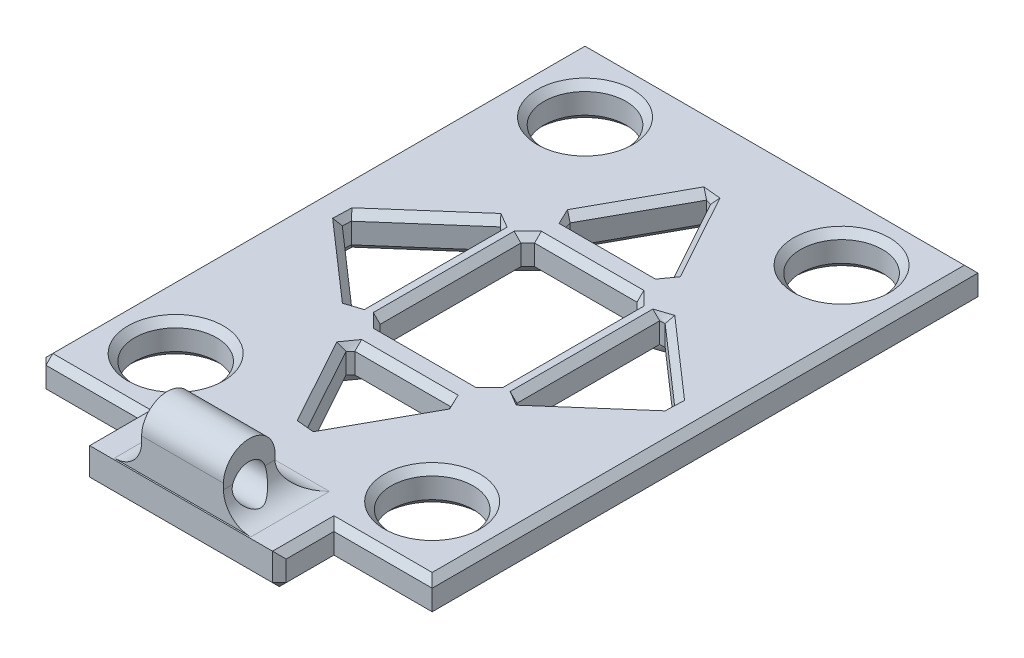
SolidWorks part; units mm, degrees
ref_plane "Front Plane" through (0, 0, 0) normal (0, 0, 1) x (1, 0, 0)
ref_plane "Top Plane" through (0, 0, 0) normal (0, 1, 0) x (1, 0, 0)
ref_plane "Right Plane" through (0, 0, 0) normal (1, 0, 0) x (0, 0, -1)
sketch "Sketch1" plane through (0, 0, 0) normal (0, 0, 1) x (1, 0, 0)
  line L1 (-18.288, 1.5875) -> (18.288, 1.5875)
  line L2 (-18.288, 1.5875) -> (-18.288, -1.5875)
  line L3 (-18.288, -1.5875) -> (18.288, -1.5875)
  line L4 (18.288, 1.5875) -> (18.288, -1.5875)
  line L5 (-18.288, 1.5875) -> (18.288, -1.5875) construction
  line L6 (-18.288, -1.5875) -> (18.288, 1.5875) construction
  point P0 (0, 0)
  dimension "D1" = 36.576
  dimension "D2" = 3.175
extrude "Boss-Extrude1" add sketch "Sketch1" along normal mid plane 50.8
sketch "Sketch2" plane through (0, 1.5875, 0) normal (0, 1, 0) x (1, 0, 0)
  line L0 (0, 25.4) -> (0, -26.1324) construction
  line L1 (-18.288, 0) -> (18.288, 0) construction
  line L4 (18.288, 25.4) -> (-18.288, 25.4)
  line L5 (-18.288, 25.4) -> (-18.288, -25.4)
  line L6 (-18.288, -25.4) -> (18.288, -25.4)
  line L7 (18.288, -25.4) -> (18.288, 25.4)
  line L8 (18.288, 25.4) -> (-18.288, 25.4)
  line L9 (-18.288, 25.4) -> (-18.288, -25.4)
  line L10 (-18.288, -25.4) -> (18.288, -25.4)
  line L11 (18.288, -25.4) -> (18.288, 25.4)
  circle A0 centre (-11.938, 19.05) radius 3.81
  circle A4 centre (-11.938, -19.05) radius 3.81
  circle A5 centre (11.938, -19.05) radius 3.81
  circle A6 centre (11.938, 19.05) radius 3.81
  point P11 (0, 0)
  dimension "D2" = 7.62
  dimension "D3" = 6.35
  dimension "D4" = 6.35
  dimension "D1" = 0
extrude "Cut-Extrude3" cut sketch "Sketch2" against normal through all contours A4 | A5 | A0 | A6
sketch "Sketch4" plane through (0, 0, 25.4) normal (0, 0, 1) x (1, 0, 0)
  line L2 (-9.144, 1.5875) -> (9.144, 1.5875)
  line L3 (-9.144, 1.5875) -> (-9.144, -1.5875)
  line L4 (18.288, -1.5875) -> (18.288, 1.5875)
  line L5 (18.288, 1.5875) -> (-18.288, 1.5875)
  line L6 (-18.288, 1.5875) -> (-18.288, -1.5875)
  line L7 (-18.288, -1.5875) -> (18.288, -1.5875)
  line L8 (18.288, -1.5875) -> (18.288, 1.5875)
  line L9 (18.288, 1.5875) -> (-18.288, 1.5875)
  line L10 (-18.288, 1.5875) -> (-18.288, -1.5875)
  line L11 (-18.288, -1.5875) -> (18.288, -1.5875)
  line L12 (-9.144, -1.5875) -> (9.144, -1.5875)
  line L13 (9.144, 1.5875) -> (9.144, -1.5875)
  line L14 (-9.144, 1.5875) -> (9.144, -1.5875) construction
  line L15 (-9.144, -1.5875) -> (9.144, 1.5875) construction
  point P3 (0, 0)
  line M6 (18.288, 1.5875) -> (-18.288, 1.5875)
  line M8 (-18.288, -1.5875) -> (18.288, -1.5875)
  dimension "D2" = 18.288
  dimension "D1" = 0
extrude "Boss-Extrude2" add sketch "Sketch4" along normal blind 5.08 contours L13 L3 M6 M8
sketch "Sketch5" plane through (0, 0, 0) normal (1, 0, 0) x (0, 0, -1)
  line L0 (-30.3441, 4.6474) -> (-30.3441, 1.5875)
  line L1 (-30.48, 1.5875) -> (-25.4, 1.5875) construction
  line L2 (-25.5515, 4.6474) -> (-25.5515, 1.5875)
  line L3 (-30.3441, 1.5875) -> (-25.5515, 1.5875)
  arc A0 (-25.5515, 4.6474) -> (-30.3441, 4.6474) centre (-27.9478, 4.6474) ccw
extrude "Boss-Extrude3" add sketch "Sketch5" along normal mid plane 7.62
sketch "Sketch6" plane through (3.81, 0, 0) normal (1, 0, 0) x (0, 0, -1)
  line L0 (-30.3441, 1.5875) -> (-25.5515, 1.5875) construction
  circle A0 centre (-27.9809, 3.6195) radius 1.5875
  dimension "D1" = 3.175
  dimension "D2" = 2.032
extrude "Cut-Extrude4" cut sketch "Sketch6" against normal blind 7.62 contours A0
fillet "Fillet1" radius 2.54 3 edges at (-3.81, 1.5875, 27.9478) (0, 1.5875, 25.5515) (3.81, 1.5875, 27.9478)
chamfer "Chamfer1" distance 0.635 angle 45 26 edges at (11.938, -1.5875, 22.86) (11.938, 1.5875, 22.86) (-11.938, 1.5875, -15.24) (-11.938, -1.5875, -15.24) (-11.938, 1.5875, 15.24) (-11.938, -1.5875, 15.24) (11.938, 1.5875, -22.86) (11.938, -1.5875, -22.86) (0, -1.5875, -25.4) (-18.288, -1.5875, 0) (-9.144, -1.5875, 27.94) (-9.144, 1.5875, 27.94) (-13.716, -1.5875, 25.4) (-18.288, 0, 25.4) (-9.144, 0, 30.48) (0, -1.5875, 30.48) (18.288, -1.5875, 0) (13.716, -1.5875, 25.4) (9.144, 1.5875, 27.94) (9.144, -1.5875, 27.94) (9.144, 0, 30.48) (13.716, 1.5875, 25.4) (18.288, 1.5875, 0) (0, 1.5875, -25.4) (-18.288, 1.5875, 0) (-13.716, 1.5875, 25.4)
sketch "Sketch7" plane through (0, 1.5875, 0) normal (0, 1, 0) x (1, 0, 0)
  line L0 (-7.3259, -7.1855) -> (-7.3259, 7.1855)
  line L1 (5.4024, -7.1855) -> (-5.4024, -7.1855)
  line L2 (5.4024, -7.1855) -> (5.4024, 7.1855)
  line L3 (5.4024, 7.1855) -> (-5.4024, 7.1855)
  line L4 (-5.4024, -7.1855) -> (-5.4024, 7.1855)
  line L5 (5.4024, -7.1855) -> (-5.4024, 7.1855) construction
  line L6 (5.4024, 7.1855) -> (-5.4024, -7.1855) construction
  line L7 (-7.3259, 7.1855) -> (-15.5323, 0)
  line L8 (-15.5323, 0) -> (-7.3259, -7.1855)
  line L9 (5.0403, 9.9058) -> (-5.0403, 9.9058)
  line L10 (-5.0403, 9.9058) -> (0, 19.0539)
  line L11 (0, 19.0539) -> (5.0403, 9.9058)
  line L12 (5.0403, 9.9058) -> (0, 19.0539)
  line L13 (16.6524, 0) -> (-17.653, 0) construction
  line L14 (-17.653, 24.765) -> (-17.653, -24.765) construction
  line L15 (0, 24.765) -> (0, -23.0115) construction
  line L16 (17.653, 24.765) -> (-17.653, 24.765) construction
  line L17 (-6.35, -23.0115) -> (6.35, -23.0115) construction
  line L18 (0, -24.765) -> (0, 23.0115) construction
  line L19 (5.0403, -9.9058) -> (0, -19.0539)
  line L20 (0, -19.0539) -> (5.0403, -9.9058)
  line L21 (-5.0403, -9.9058) -> (0, -19.0539)
  line L22 (5.0403, -9.9058) -> (-5.0403, -9.9058)
  line L23 (-16.6524, 0) -> (17.653, 0) construction
  line L24 (15.5323, 0) -> (7.3259, -7.1855)
  line L25 (7.3259, 7.1855) -> (15.5323, 0)
  line L26 (7.3259, -7.1855) -> (7.3259, 7.1855)
  point P0 (0, 0)
  point P32 (0, 0)
  point P33 (0, 0)
  point P34 (0, 0)
  point P35 (0, 0)
extrude "Cut-Extrude5" cut sketch "Sketch7" against normal blind 7.62 contours L4 L1 L2 L3 | L7 L8 L0 | L19 L22 L21 | L26 L24 L25 | L11 L10 L9
chamfer "Chamfer2" distance 0.635 angle 45 48 edges at (5.0403, 0, -9.9058) (15.5323, 0, 0) (7.3259, 0, 7.1855) (11.4291, 1.5875, 3.5927) (11.4291, 1.5875, -3.5927) (7.3259, 1.5875, 0) (7.3259, 0, -7.1855) (11.4291, -1.5875, 3.5927) (11.4291, -1.5875, -3.5927) (7.3259, -1.5875, 0) (5.0403, 0, 9.9058) (2.5202, -1.5875, 14.4799) (0, -1.5875, 9.9058) (-2.5202, -1.5875, 14.4799) (0, 0, 19.0539) (2.5202, 1.5875, 14.4799) (0, 1.5875, 9.9058) (-2.5202, 1.5875, 14.4799) (-5.0403, 0, 9.9058) (0, -1.5875, 7.1855) (0, 1.5875, 7.1855) (5.4024, -1.5875, 0) (5.4024, 0, 7.1855) (5.4024, 1.5875, 0) (0, -1.5875, -7.1855) (5.4024, 0, -7.1855) (0, 1.5875, -7.1855) (-5.4024, 0, 7.1855) (-5.4024, 1.5875, 0) (-5.4024, 0, -7.1855) (-5.4024, -1.5875, 0) (-5.0403, 0, -9.9058) (2.5202, 1.5875, -14.4799) (0, 1.5875, -9.9058) (-2.5202, 1.5875, -14.4799) (0, 0, -19.0539) (2.5202, -1.5875, -14.4799) (0, -1.5875, -9.9058) (-2.5202, -1.5875, -14.4799) (-7.3259, 0, -7.1855) (-7.3259, -1.5875, 0) (-11.4291, -1.5875, -3.5927) (-11.4291, -1.5875, 3.5927) (-7.3259, 0, 7.1855) (-7.3259, 1.5875, 0) (-11.4291, 1.5875, -3.5927) (-11.4291, 1.5875, 3.5927) (-15.5323, 0, 0)
